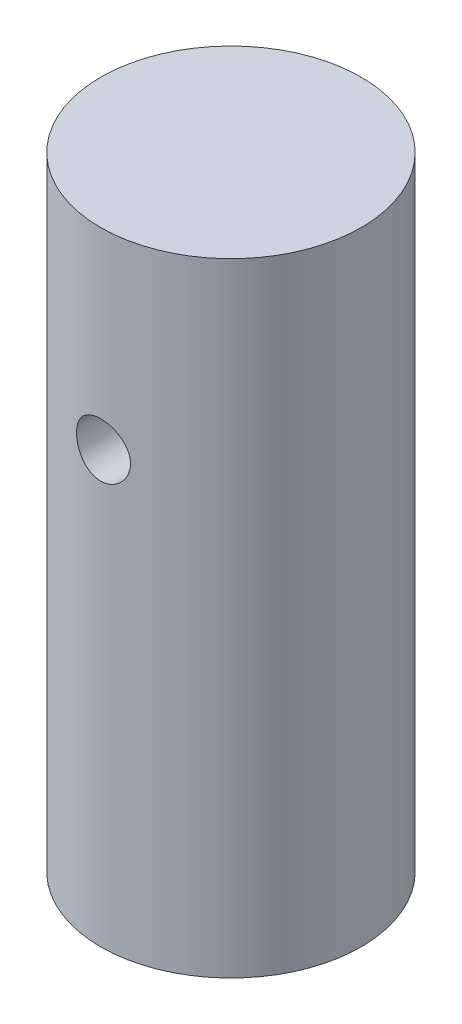
SolidWorks part; units mm, degrees
material "Gray Cast Iron"
ref_plane "Front Plane" through (0, 0, 0) normal (0, 0, 1) x (1, 0, 0)
ref_plane "Top Plane" through (0, 0, 0) normal (0, 1, 0) x (1, 0, 0)
ref_plane "Right Plane" through (0, 0, 0) normal (1, 0, 0) x (0, 0, -1)
sketch "Sketch1" plane through (0, 0, 0) normal (0, 1, 0) x (1, 0, 0)
  circle A0 centre (0, 0) radius 23
  dimension "D1" = 46
extrude "Boss-Extrude1" add sketch "Sketch1" along normal blind 110
sketch "Sketch2" plane through (0, 0, 0) normal (0, 0, 1) x (1, 0, 0)
  circle A0 centre (0, 76) radius 4.7625
  dimension "D2" = 9.525
  dimension "D1" = 76
extrude "Cut-Extrude1" cut sketch "Sketch2" against normal mid plane 50
